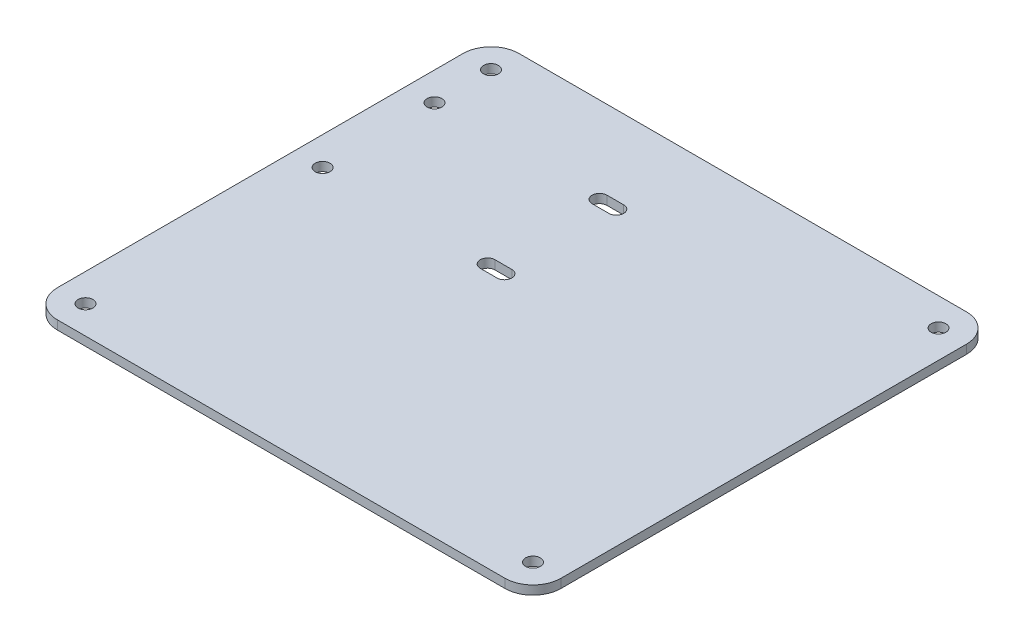
SolidWorks part; units mm, degrees
ref_plane "Front Plane" through (0, 0, 0) normal (0, 0, 1) x (1, 0, 0)
ref_plane "Top Plane" through (0, 0, 0) normal (0, 1, 0) x (1, 0, 0)
ref_plane "Right Plane" through (0, 0, 0) normal (1, 0, 0) x (0, 0, -1)
sketch "Sketch1" plane through (0, 0, 0) normal (0, 1, 0) x (1, 0, 0)
  line L1 (-90, 82.5) -> (90, 82.5)
  line L2 (-90, 82.5) -> (-90, -82.5)
  line L3 (-90, -82.5) -> (90, -82.5)
  line L4 (90, 82.5) -> (90, -82.5)
  line L5 (-90, 82.5) -> (90, -82.5) construction
  line L6 (-90, -82.5) -> (90, 82.5) construction
  point P0 (0, 0)
  dimension "D1" = 180
  dimension "D2" = 165
base flange "Base-Flange1" sketch "Sketch1" thickness 3.175 reverse thickness direction no parameters "D1"=1
fillet "Fillet1" radius 10 4 edges at (90, -1.5875, 82.5) (-90, -1.5875, 82.5) (-90, -1.5875, -82.5) (90, -1.5875, -82.5)
sketch "Sketch2" plane through (0, 0, 0) normal (0, 1, 0) x (1, 0, 0)
  line L1 (-80, -72.5) -> (80, -72.5) construction
  line L2 (-80, -72.5) -> (-80, 72.5) construction
  line L3 (-80, 72.5) -> (80, 72.5) construction
  line L4 (80, -72.5) -> (80, 72.5) construction
  line L5 (-80, -72.5) -> (80, 72.5) construction
  line L6 (-80, 72.5) -> (80, -72.5) construction
  circle A0 centre (-80, 72.5) radius 2.65
  circle A1 centre (80, 72.5) radius 2.65
  circle A2 centre (-80, -72.5) radius 2.65
  circle A3 centre (80, -72.5) radius 2.65
  point P0 (0, 0)
  dimension "D3" = 5.3
  dimension "D1" = 160
  dimension "D2" = 145
extrude "Cut-Extrude1" cut sketch "Sketch2" against normal through all normal cut yes
sketch "Sketch3" plane through (0, 0, 0) normal (0, 1, 0) x (1, 0, 0)
  line L0 (-20.4113, 51.7) -> (-14.4113, 51.7) construction
  line L1 (-20.4113, 54.35) -> (-14.4113, 54.35)
  line L2 (-20.4113, 49.05) -> (-14.4113, 49.05)
  line L3 (-20.4113, 11.7) -> (-14.4113, 11.7) construction
  line L4 (-20.4113, 14.35) -> (-14.4113, 14.35)
  line L5 (-20.4113, 9.05) -> (-14.4113, 9.05)
  circle A0 centre (-79.8175, 52.1) radius 2.65
  circle A1 centre (-79.8175, 12.1) radius 2.65
  arc A2 (-20.4113, 54.35) -> (-20.4113, 49.05) centre (-20.4113, 51.7) ccw
  arc A3 (-14.4113, 49.05) -> (-14.4113, 54.35) centre (-14.4113, 51.7) ccw
  arc A4 (-20.4113, 14.35) -> (-20.4113, 9.05) centre (-20.4113, 11.7) ccw
  arc A5 (-14.4113, 9.05) -> (-14.4113, 14.35) centre (-14.4113, 11.7) ccw
  point P8 (-17.4113, 51.7)
  point P15 (-17.4113, 11.7)
  dimension "D1" = 5.3
  dimension "D2" = 6
  dimension "D3" = 5.3
  dimension "D4" = 5.3
extrude "Cut-Extrude2" cut sketch "Sketch3" against normal through all normal cut yes
sketch "Bend-Lines1" [suppressed] plane through (0, 0, 0) normal (0, 1, 0) x (1, 0, 0)
sketch "Bounding-Box1" [suppressed] plane through (0, 0, 0) normal (0, 1, 0) x (1, 0, 0)
sheet metal parameters "Sheet-Metal1" thickness 3.175 parameters "D1"=1
flat pattern "Flat-Pattern1" [suppressed]
sketch "Bend-Lines2" plane through (0, 0, 0) normal (0, 1, 0) x (1, 0, 0)
sketch3d "Bounding-Box2" [suppressed]
  line L0 (90, -77.5, 0) -> (-90, -77.5, 0) construction
  line L1 (90, 77.5, 0) -> (-90, 77.5, 0) construction
  line L2 (90, -77.5, 0) -> (90, 77.5, 0) construction
  line L3 (-90, -77.5, 0) -> (-90, 77.5, 0) construction
sheet metal parameters "Sheet-Metal2" thickness 3.175 parameters "D1"=1
flat pattern "Flat-Pattern1"
sketch "Bend-Lines2" plane through (0, 0, 0) normal (0, 1, 0) x (1, 0, 0)
sketch3d "Bounding-Box2" [suppressed]
  line L0 (90, -82.5, 0) -> (-90, -82.5, 0) construction
  line L1 (90, 82.5, 0) -> (-90, 82.5, 0) construction
  line L2 (90, -82.5, 0) -> (90, 82.5, 0) construction
  line L3 (-90, -82.5, 0) -> (-90, 82.5, 0) construction
sheet metal parameters "Sheet-Metal4" thickness 3.175 parameters "D1"=1
flat pattern "Flat-Pattern1"
sketch "Bend-Lines2" plane through (0, 0, 0) normal (0, 1, 0) x (1, 0, 0)
sketch3d "Bounding-Box2" [suppressed]
  line L0 (90, -82.5, 0) -> (-90, -82.5, 0) construction
  line L1 (90, 82.5, 0) -> (-90, 82.5, 0) construction
  line L2 (90, -82.5, 0) -> (90, 82.5, 0) construction
  line L3 (-90, -82.5, 0) -> (-90, 82.5, 0) construction
